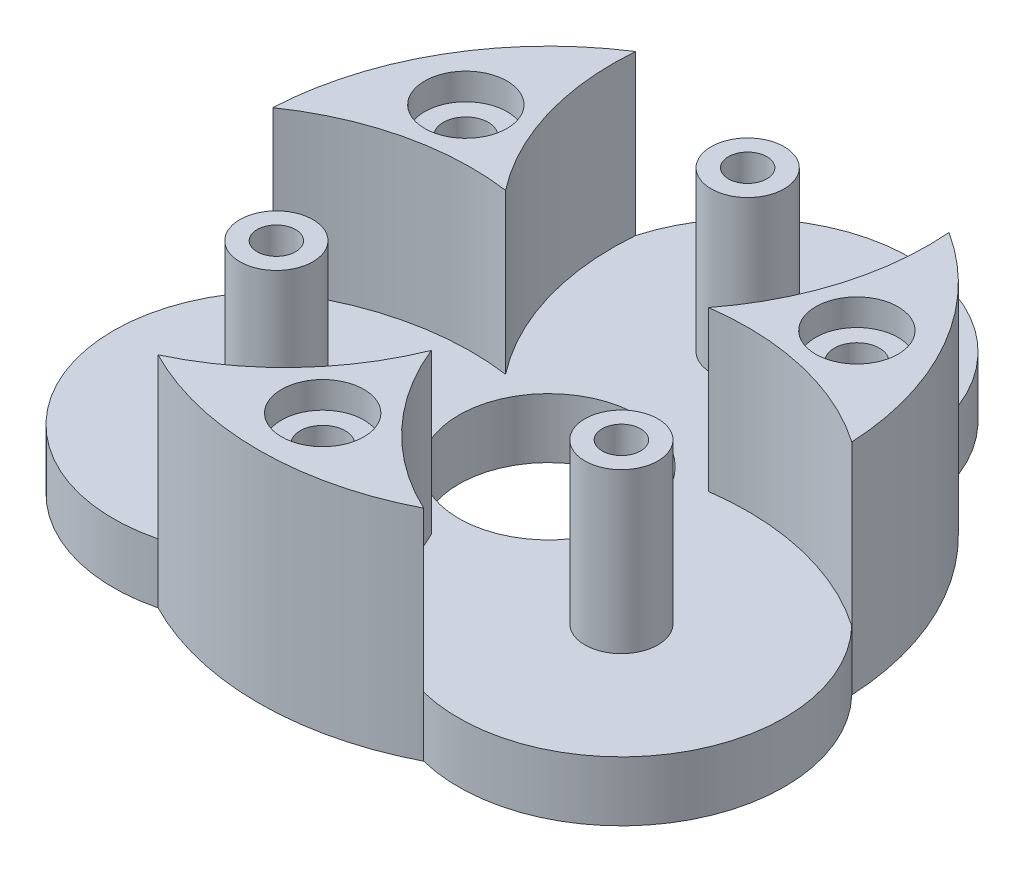
SolidWorks part; units mm, degrees
ref_plane "Alzado" through (0, 0, 0) normal (0, 0, 1) x (1, 0, 0)
ref_plane "Planta" through (0, 0, 0) normal (0, 1, 0) x (1, 0, 0)
ref_plane "Vista lateral" through (0, 0, 0) normal (1, 0, 0) x (0, 0, -1)
sketch "Croquis1" plane through (0, 0, 0) normal (0, 1, 0) x (1, 0, 0)
  circle A0 centre (0, 0) radius 5 construction
  circle A1 centre (0, 15) radius 10 construction
  circle A2 centre (0, 0) radius 25 construction
  circle A7 centre (0, 0) radius 21.825
  point P24 (0, 0)
  dimension "D1" = 10
  dimension "D2" = 20
  dimension "D3" = 43.65
extrude "Saliente-Extruir1" add sketch "Croquis1" along normal blind 4.5
sketch "Croquis2" plane through (0, 4.5, 0) normal (0, 1, 0) x (1, 0, 0)
  circle A0 centre (0, 0) radius 15 construction
  circle A1 centre (0, 15) radius 2.75
  circle A2 centre (12.9904, -7.5) radius 2.75
  circle A3 centre (-12.9904, -7.5) radius 2.75
  point P12 (0, 0)
  dimension "D1" = 30
  dimension "D2" = 5.5
  dimension "D3" = 3
extrude "Saliente-Extruir2" add sketch "Croquis2" along normal blind 12
hole_wizard "Taladro de margen para M121" positions "Croquis3" profile "Croquis4" hole size "M12" standard "ISO" end condition through all
sketch "Croquis3" plane through (0, 4.5, 0) normal (0, 1, 0) x (1, 0, 0)
  point P0 (0, 0)
sketch "Croquis4" plane through (0, 4.5, 0) normal (1, 0, 0) x (0, 0, 1)
  line L0 (0, 0) -> (0, 4.5)
  line L1 (0, 4.5) -> (6.75, 4.5)
  line L2 (6.75, 4.5) -> (6.75, 0)
  line L5 (6.75, 0) -> (0, 0)
  line L11 (0, -6.35) -> (0, 107.95) construction
  dimension "Diámetro de taladro hasta el siguiente" = 13.5
  dimension "Profundidad de taladro hasta el siguiente" = 4.5
sketch "Croquis5" plane through (0, 4.5, 0) normal (0, 1, 0) x (1, 0, 0)
  line L0 (0, 0) -> (-18.901, 10.9125) construction
  line L1 (-12.9904, -7.5) -> (0, 15) construction
  circle A0 centre (-12.9904, -7.5) radius 8.25 construction
  circle A1 centre (0, 15) radius 8.25 construction
  arc A4 (-7.6427, 4.4125) -> (-11.8002, 18.3599) centre (8.1271, 16.7067) cw
  arc A5 (-7.6427, 4.4125) -> (-21.8002, 1.0394) centre (-10.4048, -15.3916) ccw
  arc A6 (-11.8002, 18.3599) -> (-21.8002, 1.0394) centre (0, 0) ccw
  circle A7 centre (0, 0) radius 21.825 construction
  dimension "D1" = 20
  dimension "D2" = 13
extrude "Saliente-Extruir3" add sketch "Croquis5" along normal up to surface (12 mm away) up to face at (-12.9904, 16.5, 10.25)
sketch "Croquis8" plane through (0, 16.5, 0) normal (0, 1, 0) x (1, 0, 0)
  line L0 (-7.6427, 4.4125) -> (-18.901, 10.9125) construction
  circle A1 centre (-14.7224, 8.5) radius 1.7
  circle A2 centre (0, 0) radius 15 construction
  arc A3 (-11.8002, 18.3599) -> (-21.8002, 1.0394) centre (0, 0) ccw construction
  circle A4 centre (0, 0) radius 17 construction
  dimension "D1" = 3.4
  dimension "D2" = 2
extrude "Cortar-Extruir1" cut sketch "Croquis8" against normal up to surface (16.5 mm away) up to face at (0, 0, 6.75)
pattern_circular "MatrizC1" count 3 over 360 about axis through (0, 4.5, 0) along (0, 1, 0) of "Saliente-Extruir3", "Cortar-Extruir1"
hole_wizard "Taladro de margen para M2.51" positions "Croquis9" profile "Croquis10" hole size "M2.5" standard "ISO" end condition through all
sketch "Croquis9" plane through (0, 16.5, 0) normal (0, 1, 0) x (1, 0, 0)
  point P0 (12.9904, -7.5)
  point P4 (-12.9904, -7.5)
  point P7 (0, 15)
sketch "Croquis10" plane through (12.9904, 16.5, 7.5) normal (1, 0, 0) x (0, 0, 1)
  line L0 (0, 0) -> (0, 16.5)
  line L1 (0, 16.5) -> (1.45, 16.5)
  line L2 (1.45, 16.5) -> (1.45, 0)
  line L5 (1.45, 0) -> (0, 0)
  line L11 (0, -6.35) -> (0, 107.95) construction
  dimension "Diámetro de taladro hasta el siguiente" = 2.9
  dimension "Profundidad de taladro hasta el siguiente" = 16.5
sketch "Croquis11" plane through (0, 0, 0) normal (0, -1, 0) x (1, 0, 0)
  arc A0 (-10, 19.3992) -> (-21.8002, -1.0394) centre (0, 0) ccw construction
  arc A1 (-10, 19.3992) -> (-21.8002, -1.0394) centre (0, 0) ccw
  arc A2 (-21.8002, -1.0394) -> (-10, 19.3992) centre (-12.9904, 7.5) cw
  circle A3 centre (-12.9904, 7.5) radius 1.45 construction
  circle A4 centre (-12.9904, 7.5) radius 1.45 construction
extrude "Saliente-Extruir5" add sketch "Croquis11" against normal up to surface (4.5 mm away) up to face at (0, 4.5, 6.75)
pattern_circular "MatrizC2" count 3 every 120 about axis through (0, 0, 0) along (0, 1, 0) of "Saliente-Extruir5"
sketch "Croquis12" plane through (0, 0, 0) normal (0, -1, 0) x (1, 0, 0)
  circle A0 centre (-12.9904, 7.5) radius 2.875
  circle A1 centre (12.9904, 7.5) radius 2.875
  circle A2 centre (0, -15) radius 2.875
  point P10 (0, 0)
  dimension "D1" = 5.75
  dimension "D2" = 3
extrude "Cortar-Extruir2" cut sketch "Croquis12" against normal blind 2.2
sketch "Croquis13" plane through (0, 16.5, 0) normal (0, 1, 0) x (1, 0, 0)
  circle A0 centre (0, -17) radius 3.1
  circle A2 centre (-14.7224, 8.5) radius 3.1
  circle A3 centre (14.7224, 8.5) radius 3.1
  point P11 (0, 0)
  dimension "D1" = 6.2
  dimension "D2" = 3
extrude "Cortar-Extruir3" cut sketch "Croquis13" against normal blind 2
